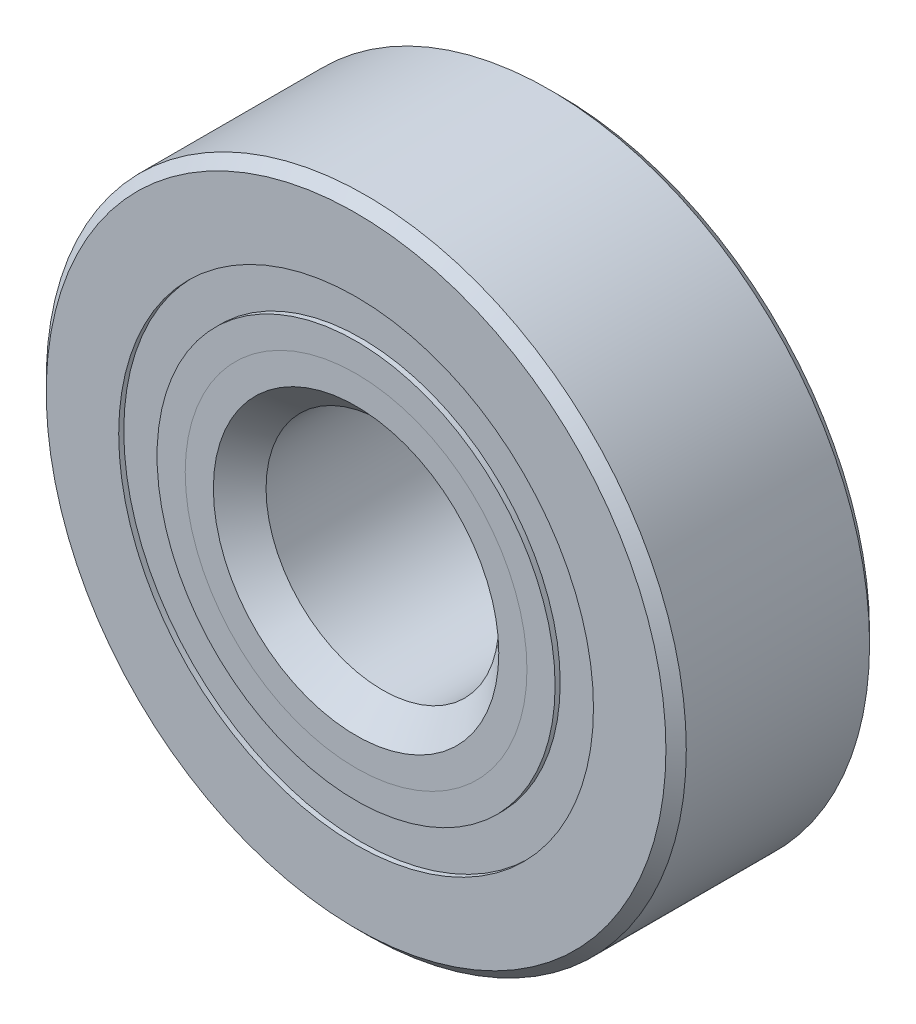
SolidWorks part; units mm, degrees
ref_plane "Front Plane" through (0, 0, 0) normal (0, 0, 1) x (1, 0, 0)
ref_plane "Top Plane" through (0, 0, 0) normal (0, 1, 0) x (1, 0, 0)
ref_plane "Right Plane" through (0, 0, 0) normal (1, 0, 0) x (0, 0, -1)
sketch "Sketch1" plane through (0, 0, 0) normal (1, 0, 0) x (0, 0, -1)
  line L0 (-5.5562, 0) -> (5.5562, 0) construction
  line L1 (0, 17.4625) -> (0, -17.4625) construction
  line L2 (5.0006, 17.4625) -> (-5.0006, 17.4625)
  line L3 (-5.0006, 17.4625) -> (-5.5563, 16.9069)
  line L4 (-5.5563, 16.9069) -> (-5.5563, 12.953)
  line L5 (-5.5563, 12.953) -> (-2.4694, 12.953)
  line L6 (5.5563, 12.953) -> (2.4694, 12.953)
  line L7 (5.5563, 16.9069) -> (5.5563, 12.953)
  line L8 (5.0006, 17.4625) -> (5.5563, 16.9069)
  line L9 (0, 17.4625) -> (0, 11.9062) construction
  line L10 (0, 11.9062) -> (0, 6.35) construction
  arc A0 (-2.4694, 12.953) -> (2.4694, 12.953) centre (0, 11.9062) cw
  point P14 (0, 6.35)
  dimension "D3" = 4.9389
  dimension "D1" = 45
  dimension "Width" = 11.1125
  dimension "OD" = 34.925
  dimension "D2" = 0.5556
  dimension "Shaft Dia" = 12.7
  dimension "D4" = 1.0467
revolve "Revolve1" add sketch "Sketch1" angle 360 about L0
sketch "Sketch2" plane through (0, 0, 0) normal (1, 0, 0) x (0, 0, -1)
  line L0 (-5.5563, 10.8595) -> (-2.4694, 10.8595)
  line L1 (-5.5563, 16.9069) -> (-5.5563, -16.9069) construction
  line L2 (-5.5563, 10.8595) -> (-5.5563, 9.3233)
  line L3 (-5.5563, 9.3233) -> (-4.02, 7.7871)
  line L4 (-4.02, 7.7871) -> (0, 7.7871)
  line L5 (0, 17.4625) -> (0, -17.4625) construction
  line L6 (0, 7.7871) -> (0, 9.2241)
  line L7 (0, 9.2241) -> (0, 6.35) construction
  line L8 (-5.5563, 10.8595) -> (-5.5563, 7.7871) construction
  line L9 (-5.5563, 7.7871) -> (-4.02, 7.7871) construction
  arc A0 (-2.4694, 10.8595) -> (0, 9.2241) centre (0, 11.9062) ccw
  arc A1 (2.4694, 12.953) -> (-2.4694, 12.953) centre (0, 11.9062) ccw construction
  circle A2 centre (0, 11.9062) radius 2.6821 construction
  dimension "D1" = 45
revolve "Revolve2" add sketch "Sketch2" angle 360 about L0
sketch "Sketch3" plane through (0, 0, 0) normal (1, 0, 0) x (0, 0, -1)
  line L0 (-5.5563, 9.3233) -> (-4.02, 7.7871)
  line L1 (-4.02, 7.7871) -> (0, 7.7871)
  line L2 (0, 7.7871) -> (0, 9.2241)
  line L3 (-5.5563, 9.3233) -> (-5.5563, 7.7871)
  line L4 (-5.5563, 10.8595) -> (-5.5563, 7.7871) construction
  line L5 (-5.5563, 7.7871) -> (-4.1192, 6.35)
  line L6 (-4.1192, 6.35) -> (5.0006, 6.35)
  line L7 (5.0006, 17.4625) -> (5.0006, -17.4625) construction
  line L8 (5.0006, 6.35) -> (5.5563, 6.9056)
  line L9 (5.5563, -16.9069) -> (5.5563, 16.9069) construction
  line L10 (5.5563, 6.9056) -> (5.5563, 10.8595)
  line L11 (5.5563, 10.8595) -> (2.4694, 10.8595)
  line L13 (5.0006, 17.4625) -> (5.5563, 16.9069) construction
  circle A0 centre (0, 11.9062) radius 2.6821 construction
  arc A1 (2.4694, 10.8595) -> (0, 9.2241) centre (0, 11.9062) cw
revolve "Revolve3" add sketch "Sketch3" angle 360 about L0
sketch "Sketch4" plane through (0, 0, 0) normal (1, 0, 0) x (0, 0, -1)
  line L0 (-2.6821, 11.9062) -> (2.6821, 11.9062)
  circle A1 centre (0, 11.9062) radius 2.6821 construction
  arc A2 (-2.6821, 11.9062) -> (2.6821, 11.9062) centre (0, 11.9062) cw
  arc A3 (2.4694, 12.953) -> (-2.4694, 12.953) centre (0, 11.9062) ccw construction
revolve "Revolve4" add sketch "Sketch4" angle 360 about L0
ref_axis "Axis1" through (0, 0, -5.5562) along (0, 0, 1)
pattern_circular "CirPattern1" count 12 every 30 about axis through (0, 0, -5.5562) along (0, 0, 1) of bodies 104
sketch "Sketch5" plane through (0, 0, 0) normal (1, 0, 0) x (0, 0, -1)
  line L0 (-5.5563, 12.953) -> (-2.4694, 12.953) construction
  line L1 (-5.2784, 12.953) -> (-2.6821, 12.953)
  line L2 (-5.2784, 12.953) -> (-5.2784, 10.8595)
  line L3 (-5.2784, 10.8595) -> (-2.6821, 10.8595)
  line L4 (-2.6821, 12.953) -> (-2.6821, 10.8595)
  line L5 (-5.5563, 10.8595) -> (-2.4694, 10.8595) construction
  line L6 (-5.0006, 17.4625) -> (-5.5563, 16.9069) construction
  line L7 (0, 17.4625) -> (0, 6.35) construction
  line L8 (5.2784, 10.8595) -> (2.6821, 10.8595)
  line L9 (2.6821, 12.953) -> (2.6821, 10.8595)
  line L10 (5.2784, 12.953) -> (2.6821, 12.953)
  line L11 (5.2784, 12.953) -> (5.2784, 10.8595)
  circle A0 centre (0, 11.9062) radius 2.6821 construction
  point P10 (-5.2784, 17.1847)
revolve "Revolve5" add sketch "Sketch5" angle 360 about L0
equation "\"D2@Sketch1\" = \"Width@Sketch1\"*.05"
equation "\"D3@Sketch1\" = \"Width@Sketch1\"/2.25"
equation "\"D4@Sketch1\" = (((\"OD@Sketch1\"-\"Width@Sketch1\")/2)/3.25)/3.5"
equation "\"D2@CirPattern1\" = 360/\"Balls@CirPattern1\""
